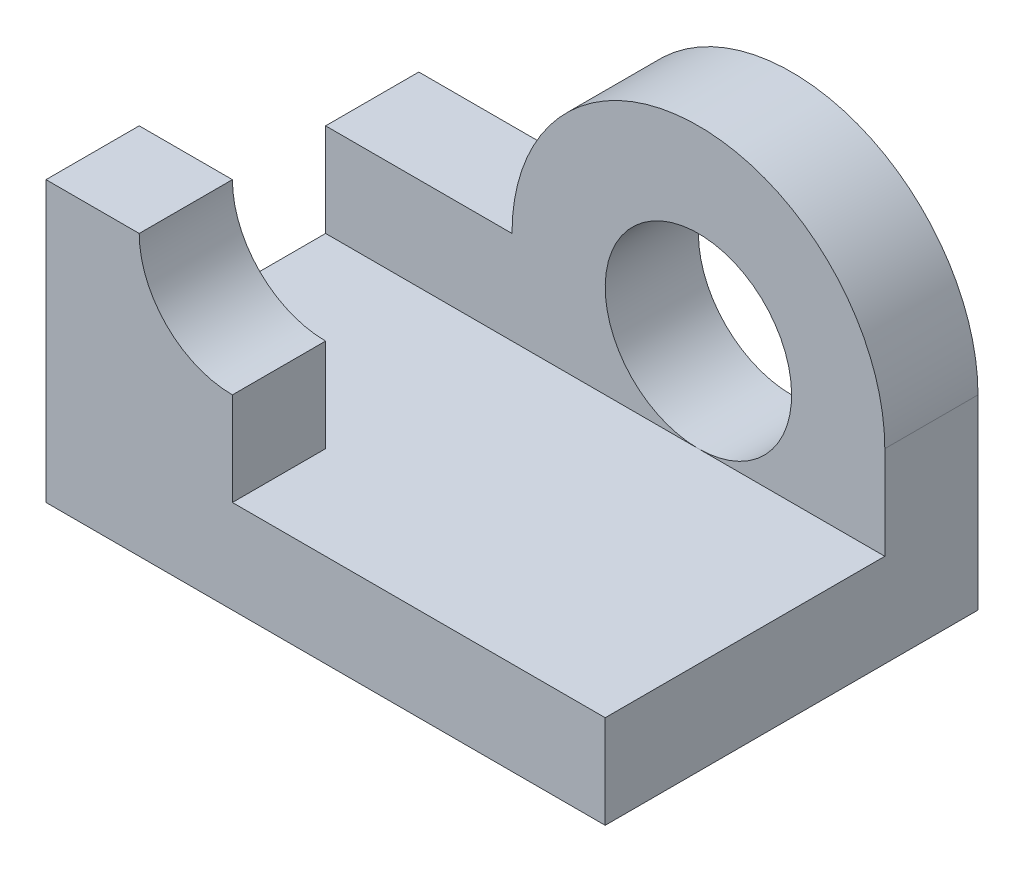
SolidWorks part; units mm, degrees
ref_plane "前基準面" through (0, 0, 0) normal (0, 0, 1) x (1, 0, 0)
ref_plane "上基準面" through (0, 0, 0) normal (0, 1, 0) x (1, 0, 0)
ref_plane "右基準面" through (0, 0, 0) normal (1, 0, 0) x (0, 0, -1)
sketch "草圖1" plane through (0, 0, 0) normal (0, 0, 1) x (1, 0, 0)
  line L0 (0, 0) -> (0, 25.6468) construction
  line L1 (0, 0) -> (-47.5247, 0) construction
  line L2 (-3.1085, 2) -> (12.6521, 2) construction
  line L3 (2, 2) -> (2, 0)
  line L4 (2, 0) -> (-4, 0)
  line L5 (-4, 0) -> (-4, 3)
  line L6 (-4, 3) -> (-3, 3)
  line L7 (-2, 1) -> (18, 1)
  line L9 (-2, 2) -> (-2, 0)
  line L10 (-2, 2) -> (-4, 2)
  line L11 (-4, 1) -> (-2, 1)
  circle A0 centre (0, 2) radius 1
  arc A1 (2, 2) -> (-2, 2) centre (0, 2) ccw
  arc A2 (-3, 3) -> (-2, 2) centre (-2, 3) ccw
  dimension "D1" = 2
  dimension "D3" = 4
  dimension "D9" = 1
  dimension "D2" = 2
  dimension "D4" = 6
  dimension "D5" = 3
  dimension "D6" = 1
  dimension "D7" = 1
  dimension "D8" = 2
extrude "填料-伸長1" add sketch "草圖1" along normal blind 1 contours L7 L9 L4 L3 | L3 A1 L9 L7 A0 | L11 L5 L4 L9 | L5 L11 L9 L10 region at (1.95, 1.5, 0) region at (0, 0.5, 0) region at (-3, 1.5, 0) region at (-3, 0.5, 0)
extrude "填料-伸長3" add sketch "草圖1<6>" along normal blind 4 contours L7 L9 L4 L3 | L11 L5 L4 L9 region at (0, 0.5, 0) region at (-3, 0.5, 0)
sketch "草圖1<6>" plane through (0, 0, 0) normal (0, 0, 1) x (1, 0, 0) same geometry as "草圖1"
extrude "填料-伸長4" add sketch "草圖1<7>" along normal blind 1 from offset 3 contours A2 L6 L5 L10 | L5 L11 L9 L10 region at (-3, 1.5, 0) region at (-3.3722, 2.4511, 0)
sketch "草圖1<7>" plane through (0, 0, 0) normal (0, 0, 1) x (1, 0, 0) same geometry as "草圖1"
